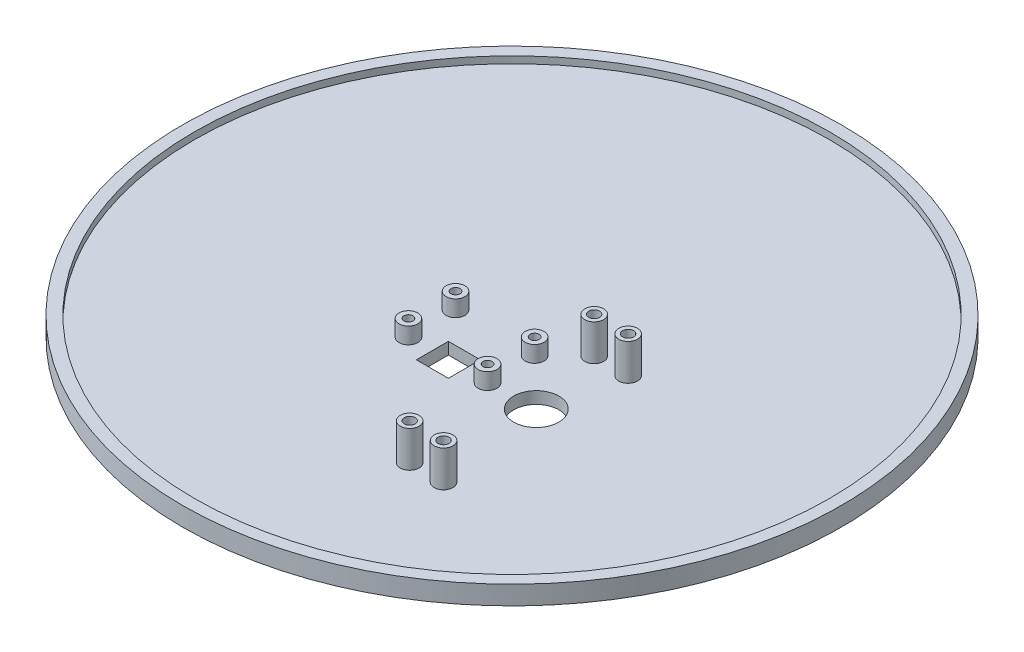
SolidWorks part; units mm, degrees
material "ABS"
ref_plane "Front Plane" through (0, 0, 0) normal (0, 0, 1) x (1, 0, 0)
ref_plane "Top Plane" through (0, 0, 0) normal (0, 1, 0) x (1, 0, 0)
ref_plane "Right Plane" through (0, 0, 0) normal (1, 0, 0) x (0, 0, -1)
sketch "Sketch1" plane through (0, 0, 0) normal (0, 1, 0) x (1, 0, 0)
  circle A0 centre (0, 0) radius 87.5
  dimension "D1" = 175
extrude "Boss-Extrude1" add sketch "Sketch1" along normal blind 5
sketch "Sketch2" plane through (0, 5, 0) normal (0, 1, 0) x (1, 0, 0)
  circle A2 centre (0, 0) radius 84.325
  circle A15 centre (0, 0) radius 87.5 construction
  point P36 (0, 0)
  dimension "D1" = 3.175
extrude "Cut-Extrude1" cut sketch "Sketch2" against normal blind 1.825
sketch "Sketch3" plane through (0, 3.175, 0) normal (0, 1, 0) x (1, 0, 0)
  line L0 (0, -16.8926) -> (0, 25.3668) construction
  line L1 (-10.5, -2.4926) -> (10.5, -2.4926) construction
  line L2 (-8.7855, -26.3546) -> (12.377, -26.3546) construction
  line L5 (4.25, -21.1426) -> (-4.25, -21.1426)
  line L6 (4.25, -21.1426) -> (4.25, -12.6426)
  line L7 (4.25, -12.6426) -> (-4.25, -12.6426)
  line L8 (-4.25, -21.1426) -> (-4.25, -12.6426)
  circle A1 centre (10.5, -16.9926) radius 1.1
  circle A2 centre (10.5, -4.4926) radius 1.1
  circle A3 centre (-10.5, -4.4926) radius 1.1
  circle A4 centre (-10.5, -16.9926) radius 1.1
  circle A5 centre (18.5, 3.3254) radius 1.25
  circle A6 centre (23, -16.5546) radius 6
  circle A7 centre (27.5, 3.3254) radius 1.25
  circle A8 centre (27.5, -45.6746) radius 1.25
  circle A9 centre (18.5, -45.6746) radius 1.25
  circle A10 centre (0, 0) radius 87.5 construction
  circle A11 centre (0, 0) radius 84.325 construction
  point P16 (0, -16.8926)
  dimension "D3" = 2.2
  dimension "D4" = 2.2
  dimension "D5" = 12.5
  dimension "D6" = 2
  dimension "D7" = 2.2
  dimension "D8" = 21
  dimension "D9" = 2.2
  dimension "D10" = 21
  dimension "D11" = 12.5
  dimension "D12" = 10.5
  dimension "D13" = 10.5
  dimension "D18" = 2.5
  dimension "D19" = 12
  dimension "D23" = 8
  dimension "D26" = 9
  dimension "D27" = 29.12
  dimension "D28" = 8
  dimension "D14" = 4.25
  dimension "D15" = 8.5
  dimension "D16" = 8.5
  dimension "D17" = 28.682
  dimension "D34" = 2
  dimension "D20" = 12.4
  dimension "D21" = 19.88
  dimension "D22" = 4.5
  dimension "D29" = 4.25
  dimension "D30" = 9.462
  dimension "D31" = 16.5546
  dimension "D32" = 26.3546
  dimension "D33" = 0
  dimension "D35" = 51.7214
  dimension "D36" = 21.1625
  dimension "D37" = 29.1162
  dimension "D24" = 2
  dimension "D25" = 2
extrude "Cut-Extrude2" cut sketch "Sketch3" against normal through all contours L8 L5 L6 L7 | A6
sketch "Sketch4" plane through (0, 3.175, 0) normal (0, 1, 0) x (1, 0, 0)
  circle A1 centre (27.5, 3.3254) radius 2.5
  circle A2 centre (27.5, -45.6746) radius 2.5
  circle A3 centre (18.5, -45.6746) radius 2.5
  circle A6 centre (10.5, -4.4926) radius 2.5
  circle A7 centre (10.5, -16.9926) radius 2.5
  circle A8 centre (-10.5, -16.9926) radius 2.5
  circle A16 centre (-10.5, -4.4926) radius 2.5
  circle A17 centre (18.5, 3.3254) radius 2.5
  dimension "D1" = 5
  dimension "D4" = 5
  dimension "D5" = 0
  dimension "D2" = 0
  dimension "D3" = 0
  dimension "D6" = 0
  dimension "D7" = 0
  dimension "D8" = 0
extrude "Boss-Extrude2" add sketch "Sketch4" along normal blind 4.325 contours A6 | A7 | A8 | A16 region at (10.5, 3.175, 4.4926) region at (10.5, 3.175, 16.9926) region at (-10.5, 3.175, 16.9926)
extrude "Boss-Extrude3" add sketch "Sketch4<2>" along normal blind 9.625 contours A1 | A3 | A2 | A3 | A17 region at (27.5, 3.175, -3.3254) region at (18.5, 3.175, 45.6746)
sketch "Sketch4<2>" plane through (0, 3.175, 0) normal (0, 1, 0) x (1, 0, 0) same geometry as "Sketch4"
hole_wizard "CSK for M2.5 Cross Countersunk Head Screw1" positions "Sketch6" profile "Sketch7" countersink size "M2.5" standard "AS" end condition through all
sketch "Sketch6" plane through (0, 0, 0) normal (0, -1, 0) x (-1, 0, 0)
  point P0 (-27.5, 3.3254)
  point P3 (-18.5, 3.3254)
  point P6 (-27.5, -45.6746)
  point P9 (-18.5, -45.6746)
  point P12 (-27.5, 3.3254)
  point P14 (-18.5, 3.3254)
  point P16 (-27.5, -45.6746)
  point P18 (-18.5, -45.6746)
sketch "Sketch7" plane through (27.5, 0, -3.3254) normal (1, 0, 0) x (0, 0, -1)
  line L0 (0, 0) -> (0, 12.8)
  line L1 (0, 12.8) -> (1.45, 12.8)
  line L2 (1.45, 12.8) -> (1.45, 1.014)
  line L3 (1.45, 1.014) -> (2.5, 0)
  line L5 (2.5, 0) -> (0, 0)
  line L6 (-1.45, 1.014) -> (-2.5, 0) construction
  line L11 (0, -6.35) -> (0, 107.95) construction
  dimension "Thru Hole Dia." = 2.9
  dimension "Thru Hole Depth" = 12.8
  dimension "Near C'Sink Dia." = 5
  dimension "Near C'Sink Angle" = 92
hole_wizard "CSK for M2 Cross Countersunk Head Screw1" positions "Sketch8" profile "Sketch9" countersink size "M2" standard "AS" end condition through all
sketch "Sketch8" plane through (0, 0, 0) normal (0, -1, 0) x (-1, 0, 0)
  point P0 (10.5, -4.4926)
  point P3 (-10.5, -4.4926)
  point P6 (-10.5, -16.9926)
  point P9 (10.5, -16.9926)
sketch "Sketch9" plane through (-10.5, 0, 4.4926) normal (1, 0, 0) x (0, 0, -1)
  line L0 (0, 0) -> (0, 12.8)
  line L1 (0, 12.8) -> (1.2, 12.8)
  line L2 (1.2, 12.8) -> (1.2, 0.7726)
  line L3 (1.2, 0.7726) -> (2, 0)
  line L5 (2, 0) -> (0, 0)
  line L6 (-1.2, 0.7726) -> (-2, 0) construction
  line L11 (0, -6.35) -> (0, 107.95) construction
  dimension "Thru Hole Dia." = 2.4
  dimension "Thru Hole Depth" = 12.8
  dimension "Near C'Sink Dia." = 4
  dimension "Near C'Sink Angle" = 92
